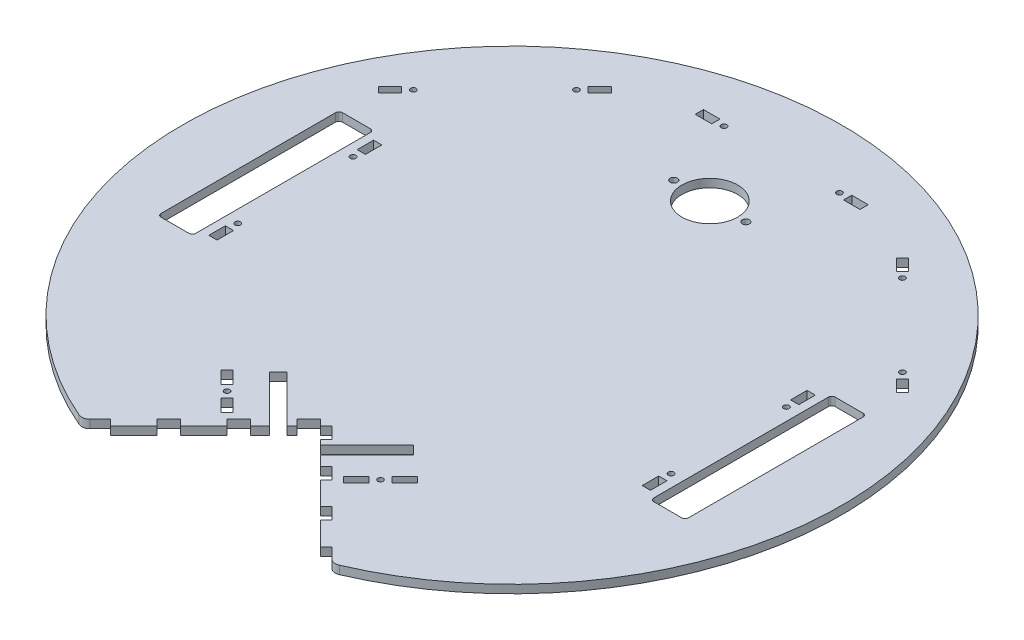
SolidWorks part; units mm, degrees
ref_plane "Front Plane" through (0, 0, 0) normal (0, 0, 1) x (1, 0, 0)
ref_plane "Top Plane" through (0, 0, 0) normal (0, 1, 0) x (1, 0, 0)
ref_plane "Right Plane" through (0, 0, 0) normal (1, 0, 0) x (0, 0, -1)
sketch "Sketch1" plane through (0, 0, 0) normal (0, 1, 0) x (1, 0, 0)
  circle A0 centre (0, 0) radius 254
  dimension "D1" = 508
extrude "Boss-Extrude1" add sketch "Sketch1" along normal blind 6.35
sketch "Sketch2" plane through (0, 6.35, 0) normal (0, 1, 0) x (1, 0, 0)
  line L0 (0, -147.7927) -> (-89.8026, -237.5952)
  line L1 (0, -36.2008) -> (0, -54.9716) construction
  line L2 (0, -147.7927) -> (89.8026, -237.5952)
  circle A0 centre (0, 0) radius 254 construction
  arc A1 (-89.8026, -237.5952) -> (89.8026, -237.5952) centre (0, 0) ccw
  dimension "D1" = 127
  dimension "D2" = 45
extrude "Cut-Extrude2" cut sketch "Sketch2" against normal through all
sketch "Sketch3" plane through (0, 6.35, 0) normal (0, 1, 0) x (1, 0, 0)
  line L0 (-31.4309, -170.2433) -> (-26.9408, -165.7532)
  line L1 (-31.4309, -170.2433) -> (-40.4112, -161.2631)
  line L2 (-26.9408, -165.7532) -> (-35.921, -156.7729)
  line L3 (-40.4112, -161.2631) -> (-35.921, -156.7729)
  line L4 (0, -147.7927) -> (-89.8026, -237.5952) construction
  line L5 (89.8026, -237.5952) -> (0, -147.7927) construction
  line L6 (-38.1661, -159.018) -> (-41.2194, -155.9647) construction
  circle A0 centre (-41.2194, -155.9647) radius 2.159
  dimension "D5" = 4.318
  dimension "D1" = 6.35
  dimension "D2" = 12.7
  dimension "D3" = 31.75
  dimension "D4" = 6.35
  dimension "D6" = 4.318
extrude "Cut-Extrude3" [suppressed] cut sketch "Sketch3" against normal through all
mirror "Mirror1" [suppressed] about plane through (0, 0, 0) normal (1, 0, 0)
sketch "Sketch4" plane through (0, 6.35, 0) normal (0, 1, 0) x (1, 0, 0)
  line L0 (0, 54.2551) -> (0, 121.7464) construction
  line L1 (-200.66, 69.85) -> (-179.07, 69.85)
  line L2 (-203.2, 67.31) -> (-203.2, -67.31)
  line L3 (-200.66, -69.85) -> (-179.07, -69.85)
  line L4 (-176.53, 67.31) -> (-176.53, -67.31)
  line L5 (-17.8666, 0) -> (24.1783, 0) construction
  line L6 (-254, -69.5481) -> (-254, -224.3367) construction
  arc A0 (-200.66, -69.85) -> (-203.2, -67.31) centre (-200.66, -67.31) cw
  arc A1 (-179.07, -69.85) -> (-176.53, -67.31) centre (-179.07, -67.31) ccw
  arc A2 (-176.53, 67.31) -> (-179.07, 69.85) centre (-179.07, 67.31) ccw
  arc A3 (-200.66, 69.85) -> (-203.2, 67.31) centre (-200.66, 67.31) ccw
  arc A4 (89.8026, -237.5952) -> (-89.8026, -237.5952) centre (0, 0) ccw construction
  dimension "D5" = 2.54
  dimension "D4" = 2.54
  dimension "D1" = 26.67
  dimension "D2" = 50.8
  dimension "D3" = 139.7
extrude "Cut-Extrude4" cut sketch "Sketch4" against normal through all
mirror "Mirror2" about plane through (0, 0, 0) normal (1, 0, 0) of "Cut-Extrude4"
sketch "Sketch6" plane through (0, 6.35, 0) normal (0, 1, 0) x (1, 0, 0)
  line L0 (-35.921, -183.7137) -> (-94.7317, -124.903) construction
  line L1 (0, -147.7927) -> (-89.8026, -237.5952) construction
  line L2 (89.8026, -237.5952) -> (0, -147.7927) construction
  line B0 (-61.3685, -153.7761) -> (-71.1005, -144.0441)
  line B1 (-61.3685, -153.7761) -> (-65.8586, -158.2663)
  line B2 (-71.1005, -144.0441) -> (-75.5906, -148.5343)
  line B3 (-65.8586, -158.2663) -> (-75.5906, -148.5343)
  line B4 (-52.3882, -162.7564) -> (-42.6562, -172.4884)
  line B5 (-56.8783, -167.2465) -> (-47.1463, -176.9785)
  line B6 (-42.6562, -172.4884) -> (-47.1463, -176.9785)
  line B7 (-52.3882, -162.7564) -> (-56.8783, -167.2465)
  circle B8 centre (-59.1234, -160.5113) radius 2.0955
  dimension "D1" = 50.8
  dimension "D2" = 12.7
sketch_block_instance "BoltTab-1"
sketch_block "BoltTab" parameters "D1"=4.191, "D2"=6.35, "D3"=6.35
extrude "Cut-Extrude6" cut sketch "Sketch6" against normal through all
mirror "Mirror5" about plane through (0, 0, 0) normal (1, 0, 0) of "Cut-Extrude6"
sketch "Sketch8" plane through (0, 0, 0) normal (0, -1, 0) x (1, 0, 0)
  line L0 (-170.18, -63.5) -> (-170.18, -50.8) construction
  line L1 (-170.18, -63.5) -> (-163.83, -63.5) construction
  line L2 (-163.83, -63.5) -> (-163.83, -50.8) construction
  line L3 (-170.18, -50.8) -> (-163.83, -50.8) construction
  line L4 (-170.18, -63.5) -> (-170.18, -50.8)
  line L5 (-170.18, -63.5) -> (-163.83, -63.5)
  line L6 (-163.83, -63.5) -> (-163.83, -50.8)
  line L7 (-170.18, -50.8) -> (-163.83, -50.8)
  line L8 (-170.18, 50.8) -> (-163.83, 50.8) construction
  line L9 (-170.18, 63.5) -> (-170.18, 50.8) construction
  line L10 (-163.83, 63.5) -> (-163.83, 50.8) construction
  line L11 (-170.18, 63.5) -> (-163.83, 63.5) construction
  line L12 (-170.18, 50.8) -> (-163.83, 50.8)
  line L13 (-170.18, 63.5) -> (-170.18, 50.8)
  line L14 (-163.83, 63.5) -> (-163.83, 50.8)
  line L15 (-170.18, 63.5) -> (-163.83, 63.5)
  line L16 (-170.18, -46.5836) -> (-163.83, -46.5836) construction
  line L17 (-170.18, -42.3164) -> (-163.83, -42.3164) construction
  line L18 (-170.18, -46.5836) -> (-163.83, -46.5836) construction
  line L19 (-170.18, -42.3164) -> (-163.83, -42.3164) construction
  line L20 (-167.005, -42.3164) -> (-167.005, -46.5836) construction
  line L21 (-170.18, 42.3164) -> (-163.83, 42.3164) construction
  line L22 (-170.18, 46.5836) -> (-163.83, 46.5836) construction
  line L23 (-170.18, 42.3164) -> (-163.83, 42.3164) construction
  line L24 (-170.18, 46.5836) -> (-163.83, 46.5836) construction
  line L25 (-167.005, 42.3164) -> (-167.005, 46.5836) construction
  circle A0 centre (-167.005, -44.45) radius 2.1336
  circle A1 centre (-167.005, 44.45) radius 2.1336
extrude "Cut-Extrude7" cut sketch "Sketch8" against normal through all
mirror "Mirror6" about plane through (0, 0, 0) normal (1, 0, 0) of "Cut-Extrude7"
sketch "Sketch9" plane through (0, 0, 0) normal (0, -1, 0) x (1, 0, 0)
  line L0 (-63.5, -204.6423) -> (-63.5, -210.9923) construction
  line L1 (-63.5, -204.6423) -> (-50.8, -204.6423) construction
  line L2 (-50.8, -204.6423) -> (-50.8, -210.9923) construction
  line L3 (-63.5, -210.9923) -> (-50.8, -210.9923) construction
  line L4 (-63.5, -204.6423) -> (-63.5, -210.9923)
  line L5 (-63.5, -204.6423) -> (-50.8, -204.6423)
  line L6 (-50.8, -204.6423) -> (-50.8, -210.9923)
  line L7 (-63.5, -210.9923) -> (-50.8, -210.9923)
  line L8 (-46.5836, -204.6423) -> (-46.5836, -210.9923) construction
  line L9 (-42.3164, -204.6423) -> (-42.3164, -210.9923) construction
  line L10 (-46.5836, -204.6423) -> (-46.5836, -210.9923) construction
  line L11 (-42.3164, -204.6423) -> (-42.3164, -210.9923) construction
  line L12 (-46.5836, -207.8173) -> (-42.3164, -207.8173) construction
  line L13 (42.3164, -204.6423) -> (42.3164, -210.9923) construction
  line L14 (46.5836, -204.6423) -> (46.5836, -210.9923) construction
  line L15 (42.3164, -204.6423) -> (42.3164, -210.9923) construction
  line L16 (46.5836, -204.6423) -> (46.5836, -210.9923) construction
  line L17 (50.8, -210.9923) -> (63.5, -210.9923)
  line L18 (63.5, -210.9923) -> (63.5, -204.6423)
  line L19 (63.5, -204.6423) -> (50.8, -204.6423)
  line L20 (50.8, -204.6423) -> (50.8, -210.9923)
  line L21 (50.8, -210.9923) -> (63.5, -210.9923)
  line L22 (63.5, -210.9923) -> (63.5, -204.6423)
  line L23 (63.5, -204.6423) -> (50.8, -204.6423)
  line L24 (50.8, -204.6423) -> (50.8, -210.9923)
  line L25 (42.3164, -207.8173) -> (46.5836, -207.8173) construction
  circle A0 centre (-44.45, -207.8173) radius 2.1336
  circle A1 centre (44.45, -207.8173) radius 2.1336
  dimension "D1" = 0
extrude "Cut-Extrude8" cut sketch "Sketch9" against normal through all
sketch "Sketch10" plane through (0, 0, 0) normal (0, -1, 0) x (1, 0, 0)
  line L0 (-204.1857, -101.143) -> (-195.2055, -110.1232) construction
  line L1 (-195.2055, -110.1232) -> (-190.7153, -105.6331) construction
  line L2 (-190.7153, -105.6331) -> (-199.6956, -96.6529) construction
  line L3 (-199.6956, -96.6529) -> (-204.1857, -101.143) construction
  line L4 (-123.3634, -181.9653) -> (-114.3832, -190.9455) construction
  line L5 (-114.3832, -190.9455) -> (-109.893, -186.4554) construction
  line L6 (-109.893, -186.4554) -> (-118.8733, -177.4752) construction
  line L7 (-118.8733, -177.4752) -> (-123.3634, -181.9653) construction
  line L8 (-204.1857, -101.143) -> (-195.2055, -110.1232)
  line L9 (-195.2055, -110.1232) -> (-190.7153, -105.6331)
  line L10 (-190.7153, -105.6331) -> (-199.6956, -96.6529)
  line L11 (-199.6956, -96.6529) -> (-204.1857, -101.143)
  line L12 (-123.3634, -181.9653) -> (-114.3832, -190.9455)
  line L13 (-114.3832, -190.9455) -> (-109.893, -186.4554)
  line L14 (-109.893, -186.4554) -> (-118.8733, -177.4752)
  line L15 (-118.8733, -177.4752) -> (-123.3634, -181.9653)
  line L16 (-187.7339, -108.6146) -> (-192.224, -113.1047) construction
  line L17 (-184.7165, -111.6319) -> (-189.2067, -116.122) construction
  line L18 (-124.8721, -171.4763) -> (-129.3622, -175.9665) construction
  line L19 (-121.8547, -174.4937) -> (-126.3449, -178.9838) construction
  line L20 (-187.7339, -108.6146) -> (-192.224, -113.1047) construction
  line L21 (-184.7165, -111.6319) -> (-189.2067, -116.122) construction
  line L22 (-124.8721, -171.4763) -> (-129.3622, -175.9665) construction
  line L23 (-121.8547, -174.4937) -> (-126.3449, -178.9838) construction
  line L25 (-186.9616, -113.877) -> (-189.979, -110.8596) construction
  line L26 (-127.1172, -173.7214) -> (-124.0998, -176.7388) construction
  circle A0 centre (-188.4703, -112.3683) radius 2.1336
  circle A1 centre (-125.6085, -175.2301) radius 2.1336
extrude "Cut-Extrude9" cut sketch "Sketch10" against normal through all
mirror "Mirror7" about plane through (0, 0, 0) normal (1, 0, 0) of "Cut-Extrude9"
sketch "Sketch11" plane through (0, 6.35, 0) normal (0, 1, 0) x (1, 0, 0)
  line L0 (0, 61.4305) -> (0, 100.7164) construction
  line L1 (-82.8279, 254) -> (68.7629, 254) construction
  circle A0 centre (0, 152.4) radius 21.463
  arc A1 (89.8026, -237.5952) -> (-89.8026, -237.5952) centre (0, 0) ccw construction
  circle A2 centre (27.7813, 152.4) radius 2.7781 construction
  circle A3 centre (-27.7813, 152.4) radius 2.7781 construction
  circle A4 centre (27.7813, 152.4) radius 2.7781
  circle A5 centre (-27.7813, 152.4) radius 2.7781
  dimension "D1" = 42.926
  dimension "D2" = 101.6
extrude "Cut-Extrude10" cut sketch "Sketch11" against normal through all
sketch "Sketch12" plane through (73.8963, 0, 73.8963) normal (0.7071, 0, 0.7071) x (0.7071, 0, -0.7071)
  line L0 (-218.8052, 6.35) -> (-218.8052, 0) construction
  line L1 (-244.2052, 6.35) -> (-218.8052, 6.35)
  line L2 (-244.2052, 6.35) -> (-244.2052, 0)
  line L3 (-244.2052, 0) -> (-218.8052, 0)
  line L4 (-218.8052, 6.35) -> (-218.8052, 0)
  line L5 (-104.5052, 0) -> (-231.5052, 0) construction
  line L6 (-104.5052, 6.35) -> (-231.5052, 6.35) construction
  line L7 (-193.4052, 6.35) -> (-180.7052, 6.35)
  line L8 (-193.4052, 6.35) -> (-193.4052, 0)
  line L9 (-193.4052, 0) -> (-180.7052, 0)
  line L10 (-180.7052, 6.35) -> (-180.7052, 0)
  line L11 (-193.4052, 0) -> (-193.4052, 6.35) construction
  line L12 (-180.7052, 6.35) -> (-180.7052, 0) construction
  line L13 (-155.3052, 0) -> (-155.3052, 6.35) construction
  line L14 (-155.3052, 6.35) -> (-142.6052, 6.35)
  line L15 (-155.3052, 6.35) -> (-155.3052, 0)
  line L16 (-155.3052, 0) -> (-142.6052, 0)
  line L17 (-142.6052, 6.35) -> (-142.6052, 0)
  line L18 (-142.6052, 6.35) -> (-142.6052, 0) construction
  line L19 (-117.2052, 0) -> (-117.2052, 6.35) construction
  line L20 (-117.2052, 6.35) -> (-104.5052, 6.35)
  line L21 (-117.2052, 6.35) -> (-117.2052, 0)
  line L22 (-117.2052, 0) -> (-104.5052, 0)
  line L23 (-104.5052, 6.35) -> (-104.5052, 0)
  dimension "D1" = 25.4
extrude "Cut-Extrude11" cut sketch "Sketch12" against normal blind 6.35
mirror "Mirror8" about plane through (0, 0, 0) normal (1, 0, 0) of "Cut-Extrude11"
fillet "Fillet1" radius 6.35 2 edges at (96.2464, 3.175, 235.0588) (-96.2464, 3.175, 235.0588)
sketch "Sketch13" plane through (0, 6.35, 0) normal (0, 1, 0) x (1, 0, 0)
  line L0 (-12.8175, -160.6102) -> (-19.5414, -167.3341)
  line L1 (-12.8175, -160.6102) -> (-48.7385, -124.6892)
  line L2 (-19.5414, -167.3341) -> (-55.4624, -131.4131)
  line L3 (-48.7385, -124.6892) -> (-55.4624, -131.4131)
  line L4 (-13.4704, -152.2828) -> (-8.9803, -156.7729) construction
  line L8 (-8.9803, -156.7729) -> (-26.9408, -174.7335) construction
  line L10 (-18.2288, -161.9228) -> (-23.4806, -156.671) construction
  line L11 (-141023.2885, 140843.1369) -> (176159.4344, -176339.586) construction
  dimension "D1" = 50.8
extrude "Cut-Extrude12" cut sketch "Sketch13" against normal through all
mirror "Mirror9" about plane through (0, 0, 0) normal (1, 0, 0) of "Cut-Extrude12"
